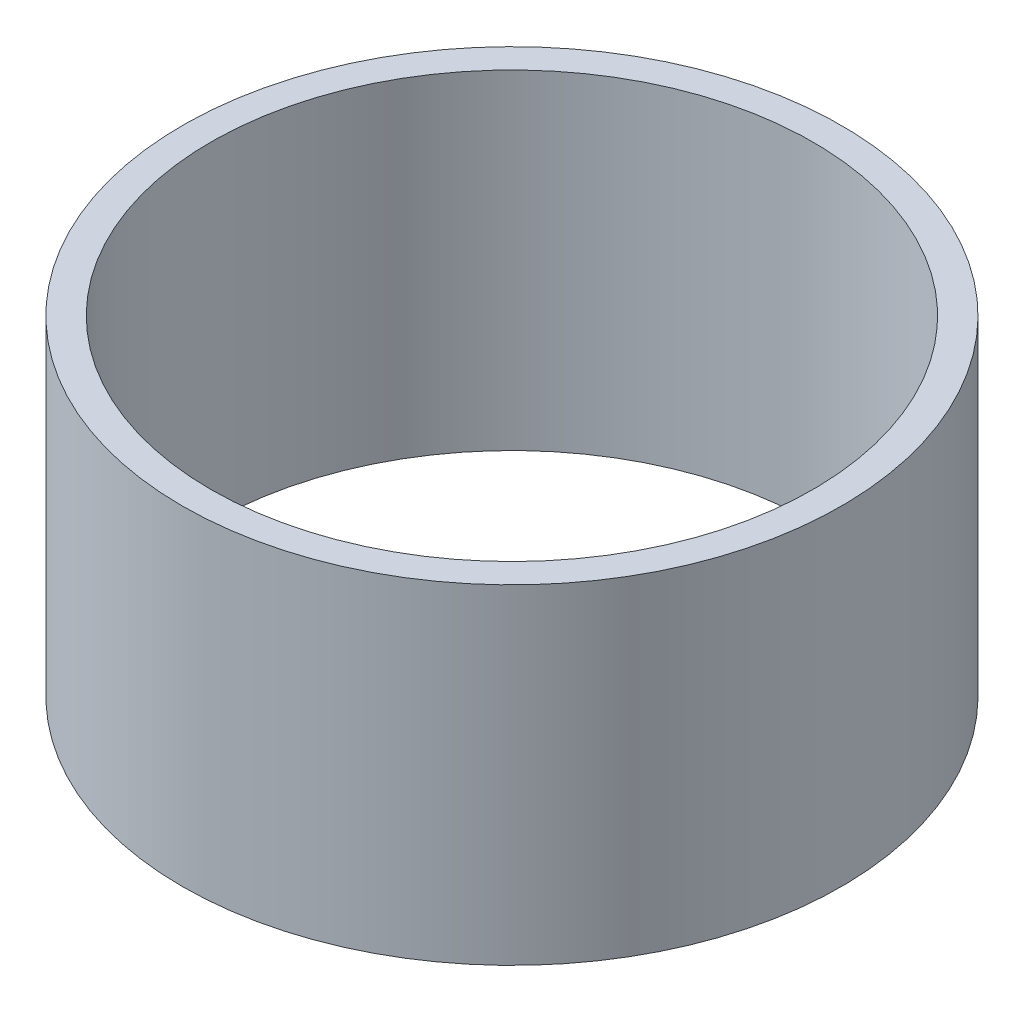
SolidWorks part; units mm, degrees
ref_plane "Front Plane" through (0, 0, 0) normal (0, 0, 1) x (1, 0, 0)
ref_plane "Top Plane" through (0, 0, 0) normal (0, 1, 0) x (1, 0, 0)
ref_plane "Right Plane" through (0, 0, 0) normal (1, 0, 0) x (0, 0, -1)
sketch "Sketch1" plane through (0, 0, 0) normal (0, 1, 0) x (1, 0, 0)
  circle A0 centre (0, 0) radius 19.05
extrude "Extrude1" add sketch "Sketch1" along normal blind 9.525 and the other way blind 9.525
sketch "Sketch2" plane through (0, 0, 0) normal (0, 1, 0) x (1, 0, 0)
  circle A0 centre (0, 0) radius 17.399
  dimension "D1" = 34.798
extrude "Cut-Extrude1" cut sketch "Sketch2" against normal through all and the other way through all
